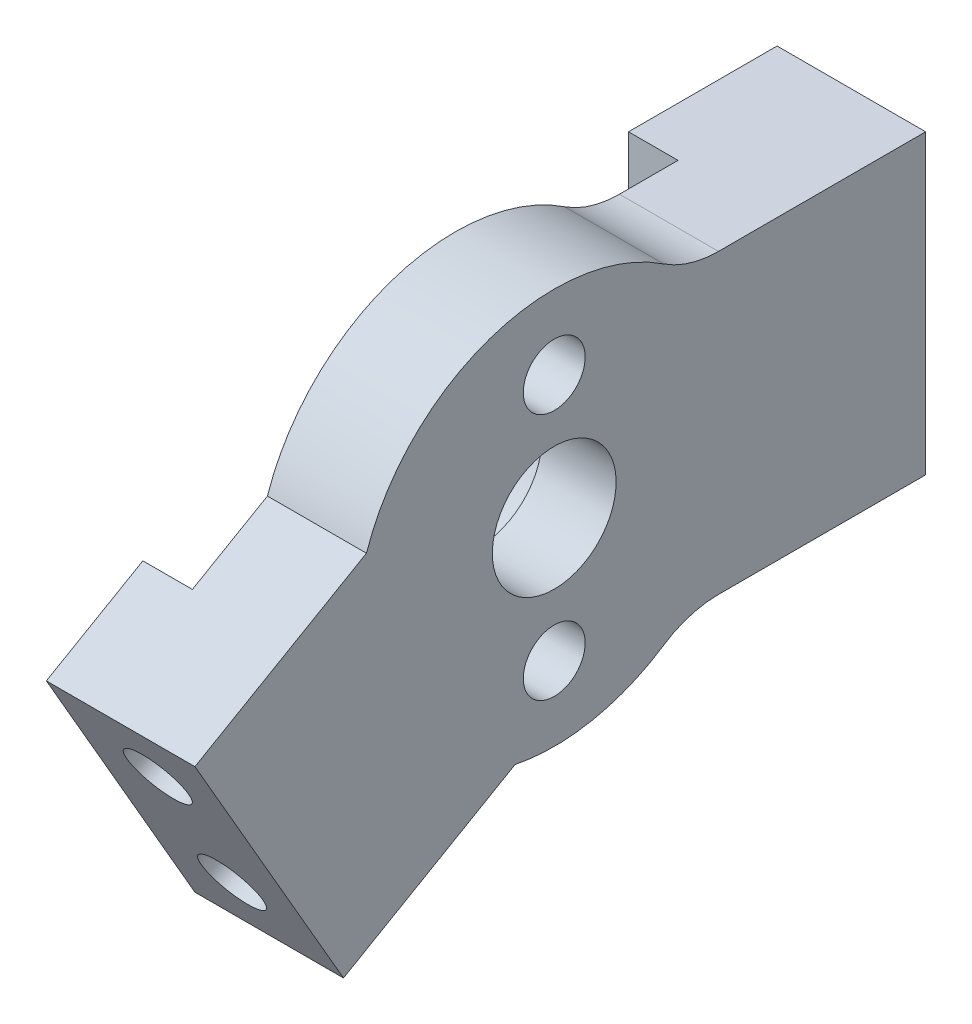
SolidWorks part; units mm, degrees
note: '?' marks a value the reader was unsure of.
ref_plane "Front" through (0, 0, 0) normal (0, 0, 1) x (1, 0, 0)
ref_plane "Top" through (0, 0, 0) normal (0, 1, 0) x (1, 0, 0)
ref_plane "Right" through (0, 0, 0) normal (1, 0, 0) x (0, 0, -1)
sketch "Sketch1" plane through (0, 0, 0) normal (0, 0, 1) x (1, 0, 0)
  line L1 (-4, 6) -> (2, 6)
  line L2 (-4, 6) -> (-4, -6)
  line L3 (-4, -6) -> (2, -6)
  line L4 (2, 6) -> (2, -6)
  dimension "D1" = 6
  dimension "D2" = 6
  dimension "D3" = 4
  dimension "D4" = 2
extrude "Extrude1" add sketch "Sketch1" along normal blind 6
sketch "Sketch2" plane through (0, 0, 0) normal (0, 0, -1) x (-1, 0, 0)
  line L0 (-2, 6) -> (4, 6) construction
  line L1 (4, -6) -> (-2, -6) construction
  line L2 (4, 6) -> (4, -6) construction
  circle A0 centre (1, 3) radius 1.25
  circle A1 centre (1, -3) radius 1.25
  dimension "D2" = 2.5
  dimension "D3" = 2.5
  dimension "D1" = 3
  dimension "D4" = 3
  dimension "D5" = 3
sketch "Sketch3" plane through (0, 0, 6) normal (0, 0, 1) x (1, 0, 0)
  line L1 (-2, 4.3) -> (2, 4.3)
  line L2 (-2, 4.3) -> (-2, -4.3)
  line L3 (-2, -4.3) -> (2, -4.3)
  line L4 (2, 4.3) -> (2, -4.3)
  dimension "D1" = 2
  dimension "D2" = 2
  dimension "D3" = 4.3
  dimension "D4" = 4.3
extrude "Extrude2" add sketch "Sketch3" along normal blind 1
extrude "Extrude3" cut sketch "Sketch2" against normal blind 5.5
cosmetic thread "Hole Thread1" parameters "D1"=4.5, "D2"=3
cosmetic thread "Hole Thread2" parameters "D1"=4.5, "D2"=3
cosmetic thread "Hole Thread3" parameters "D1"=4.5, "D2"=3
cosmetic thread "Hole Thread4" parameters "D1"=4.5, "D2"=3
cosmetic thread "Hole Thread7" parameters "D1"=4.5, "D2"=3
cosmetic thread "Hole Thread8" parameters "D1"=4.5, "D2"=3
cosmetic thread "Hole Thread11" parameters "D1"=4.5, "D2"=3
cosmetic thread "Hole Thread12" parameters "D1"=4.5, "D2"=3
cosmetic thread "Hole Thread13" parameters "D1"=4.5, "D2"=3
cosmetic thread "Hole Thread14" parameters "D1"=4.5, "D2"=3
cosmetic thread "Hole Thread15" parameters "D1"=4, "D2"=3
cosmetic thread "Hole Thread16" parameters "D1"=4, "D2"=3
cosmetic thread "Hole Thread17" parameters "D1"=3.5, "D2"=3
cosmetic thread "Hole Thread18" parameters "D1"=3.5, "D2"=3
cosmetic thread "Hole Thread19" parameters "D1"=3, "D2"=3
cosmetic thread "Hole Thread20" parameters "D1"=3, "D2"=3
cosmetic thread "Hole Thread21" parameters "D1"=3, "D2"=3
cosmetic thread "Hole Thread22" parameters "D1"=3, "D2"=3
cosmetic thread "Hole Thread23" parameters "D1"=2, "D2"=3
cosmetic thread "Hole Thread24" parameters "D1"=2, "D2"=3
cosmetic thread "Hole Thread25" parameters "D1"=2, "D2"=3
cosmetic thread "Hole Thread26" parameters "D1"=2, "D2"=3
sketch "Sketch4" plane through (2, 0, 0) normal (1, 0, 0) x (0, 0, -1)
  line L0 (-9.7085, 6) -> (-6, 6)
  line L1 (-7, -4.3) -> (-7, 4.3) construction
  line L2 (-6, 6) -> (-6, -6)
  line L3 (-6, -6) -> (-9.7085, -6)
  arc A0 (-9.7085, 6) -> (-9.7085, -6) centre (-15, 0) ccw
  dimension "D2" = 8
  dimension "D1" = 8
extrude "Extrude4" add sketch "Sketch4" against normal blind 4
sketch "Sketch6" plane through (-2, 0, 0) normal (-1, 0, 0) x (0, 0, 1)
  circle A0 centre (15, 0) radius 3
  dimension "D1" = 6
extrude "Extrude5" cut sketch "Sketch6" against normal blind 1
ref_axis "Axis1" through (-1, 0, 15) along (-1, 0, 0)?
sketch "Sketch7" plane through (-2, 0, 0) normal (-1, 0, 0) x (0, 0, 1)
  circle A0 centre (15, -5) radius 1.25
  circle A2 centre (15, 5) radius 1.25
  circle A3 centre (15, 0) radius 3 construction
  dimension "D1" = 2.5
  dimension "D3" = 2.5
  dimension "D4" = 5
  dimension "D2" = 5
extrude "Extrude6" cut sketch "Sketch7" against normal up to surface (4 mm away) up to face at (2, 0, 8.1771)
sketch "Sketch8" plane through (-1, 0, 0) normal (-1, 0, 0) x (0, 0, 1)
  circle A0 centre (15, 0) radius 2.5
  dimension "D1" = 5
extrude "Extrude7" cut sketch "Sketch8" against normal up to surface (3 mm away) up to face at (2, 3.75, 15)
fillet "Fillet1" radius 4 2 edges at (0, 6, 9.7085) (0, -6, 9.7085)
sketch "Sketch12" plane through (-2, 0, 0) normal (-1, 0, 0) x (0, 0, 1)
  line L0 (23.5108, -11.8419) -> (16.5826, -7.8419)
  line L1 (29.5108, -1.4496) -> (22.5826, 2.5504)
  line L2 (29.5108, -1.4496) -> (23.5108, -11.8419)
  line L3 (6, -6) -> (0, -6) construction
  arc A0 (10.5778, -6.6667) -> (10.5778, 6.6667) centre (15, 0) ccw construction
  circle A1 centre (15, 0) radius 2.5 construction
  arc A2 (22.5826, 2.5504) -> (16.5826, -7.8419) centre (15, 0) cw
  arc M7 (10.5778, -6.6667) -> (10.5778, 6.6667) centre (15, 0) ccw
  dimension "D2" = 6
  dimension "D1" = 12
  dimension "D3" = 8
  dimension "D4" = 8
  dimension "D5" = 150
extrude "Extrude9" add sketch "Sketch12" against normal up to surface (4 mm away) contours L2 L1 L0 M7 up to face at (2, -2.5, 15)
sketch "Sketch13" plane through (-2, 0, 0) normal (-1, 0, 0) x (0, 0, 1)
  line L0 (29.5108, -1.4496) -> (25.6137, 0.8004)
  line L1 (29.5108, -1.4496) -> (22.5826, 2.5504) construction
  line L2 (25.6137, 0.8004) -> (19.6137, -9.5919)
  line L3 (23.5108, -11.8419) -> (16.5826, -7.8419) construction
  line L4 (19.6137, -9.5919) -> (23.5108, -11.8419)
  line L5 (23.5108, -11.8419) -> (29.5108, -1.4496)
  dimension "D1" = 4.5
extrude "Extrude10" add sketch "Sketch13" along normal up to surface (2 mm away) up to face at (-4, 0, 3)
sketch "Sketch14" plane through (0, -13.1409, 22.7608) normal (0, -0.5, 0.866) x (1, 0, 0)
  line L0 (-4, 13.5) -> (-4, 1.5) construction
  line L2 (2, 13.5) -> (-4, 13.5) construction
  line L3 (2, 1.5) -> (-4, 1.5) construction
  circle A0 centre (-1, 4.5) radius 1.25
  circle A1 centre (-1, 10.5) radius 1.25
  dimension "D1" = 2.5
  dimension "D2" = 2.5
  dimension "D3" = 3
  dimension "D4" = 3
  dimension "D5" = 3
  dimension "D6" = 3
extrude "Extrude11" cut sketch "Sketch14" against normal blind 4
cosmetic thread "Hole Thread5" parameters "D1"=4, "D2"=3
cosmetic thread "Hole Thread6" parameters "D1"=4, "D2"=3
